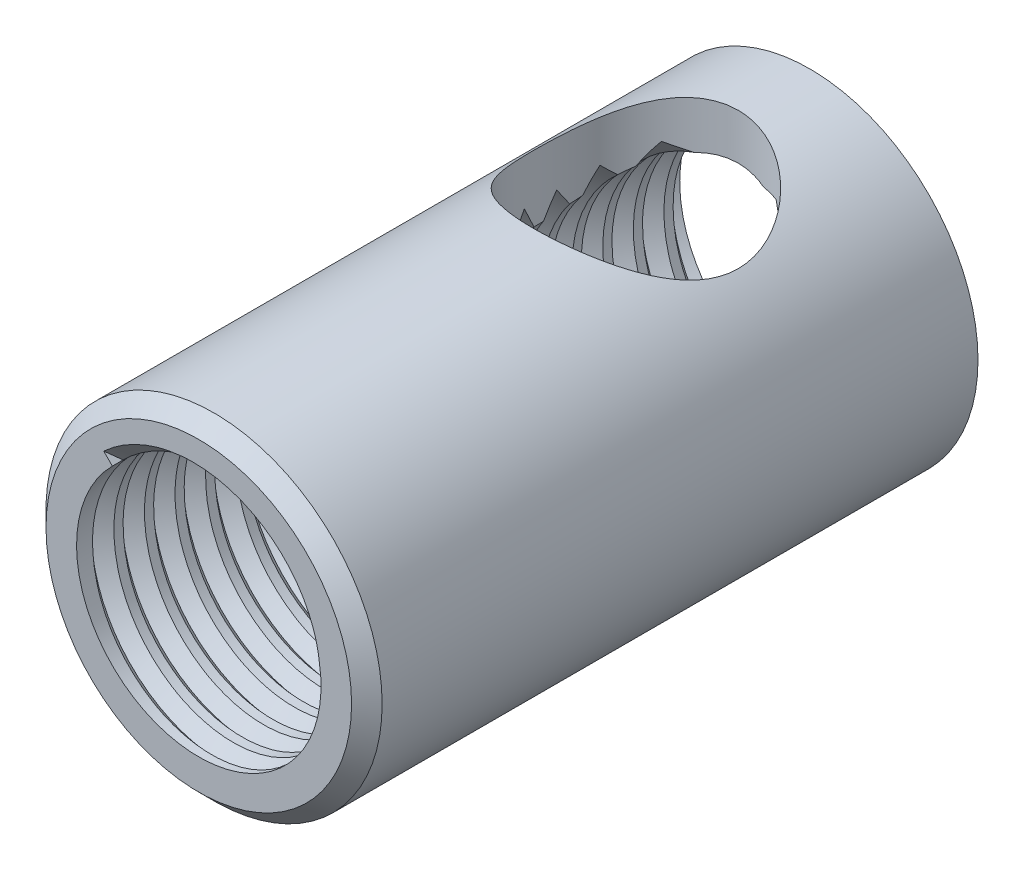
SolidWorks part; units mm, degrees
note: The reader was unsure of these and kept them because the rebuilt part matched: shared geometry of "草图5<2>".
ref_plane "前视基准面" through (0, 0, 0) normal (0, 0, 1) x (1, 0, 0)
ref_plane "上视基准面" through (0, 0, 0) normal (0, 1, 0) x (1, 0, 0)
ref_plane "右视基准面" through (0, 0, 0) normal (1, 0, 0) x (0, 0, -1)
sketch "草图1" plane through (0, 0, 0) normal (0, 0, 1) x (1, 0, 0)
  circle A0 centre (0, 0) radius 5.5
  dimension "D1" = 11
extrude "凸台-拉伸1" add sketch "草图1" along normal blind 20
chamfer "倒角1" distance 0.5 angle 45 1 edges at (5.5, 0, 20)
sketch "草图2" plane through (0, 0, 20) normal (0, 0, 1) x (1, 0, 0)
  circle A0 centre (0, 0) radius 4
  dimension "D1" = 8
extrude "切除-拉伸1" cut sketch "草图2" against normal through all
sketch "草图3" plane through (0, 0, 20) normal (0, 0, 1) x (1, 0, 0)
  circle A0 centre (0, 0) radius 4
curve "螺旋线/涡状线1" pitch 1 height 20 turns 20
sketch "草图4" plane through (0, 0, 0) normal (0, 1, 0) x (1, 0, 0)
  line L0 (4, -19.275) -> (4, -19.975)
  line L1 (4, -19.625) -> (4.4, -19.625) construction
  line L2 (4, -19.275) -> (4.4, -19.625)
  line L3 (4, -19.975) -> (4.4, -19.625)
  dimension "D1" = 0.7
  dimension "D2" = 0.4
sweep "切除-扫描1" cut profiles "草图4" path "螺旋线/涡状线1"
sketch "草图5" plane through (0, 0, 0) normal (0, 1, 0) x (1, 0, 0)
  circle A0 centre (0, -5.6952) radius 3.35
  dimension "D1" = 6.7
extrude "切除-拉伸2" cut sketch "草图5" against normal through all
extrude "切除-拉伸3" cut sketch "草图5<2>" along normal blind 20
sketch "草图5<2>" plane through (0, 0, 0) normal (0, 1, 0) x (1, 0, 0) same geometry as "草图5"
